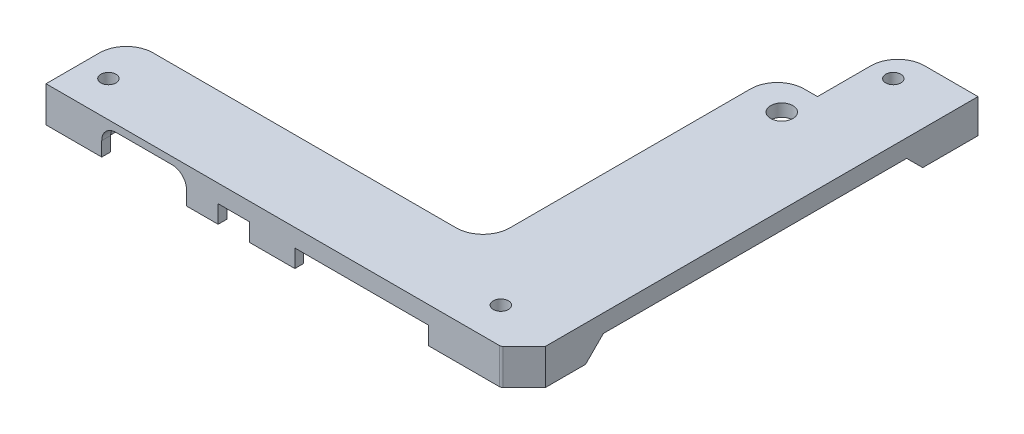
SolidWorks part; units mm, degrees
ref_plane "前视基准面" through (0, 0, 0) normal (0, 0, 1) x (1, 0, 0)
ref_plane "上视基准面" through (0, 0, 0) normal (0, 1, 0) x (1, 0, 0)
ref_plane "右视基准面" through (0, 0, 0) normal (1, 0, 0) x (0, 0, -1)
sketch "草图2" plane through (0, 0, 0) normal (0, 1, 0) x (1, 0, 0)
  line L0 (40, 41) -> (44.5, 41)
  line L1 (0, 0) -> (53.5, 0)
  line L2 (0, 0) -> (0, 8)
  line L3 (0, 8) -> (40, 8)
  line L6 (40, 8) -> (40, 41)
  line L7 (44.5, 50) -> (53.5, 50)
  line L8 (53.5, 0) -> (53.5, 50)
  line L9 (44.5, 41) -> (44.5, 50)
  dimension "D1" = 53.5
  dimension "D2" = 8
  dimension "D3" = 13.5
  dimension "D4" = 50
  dimension "D5" = 9
  dimension "D6" = 9
extrude "凸台-拉伸1" add sketch "草图2" along normal blind 2
sketch "草图3" plane through (0, 0, 0) normal (0, -1, 0) x (1, 0, 0)
  line L0 (0, 0) -> (53.5, 0) construction
  line L1 (6.25, 0) -> (15.75, 0)
  line L2 (6.25, 0) -> (6.25, -8)
  line L3 (6.25, -8) -> (15.75, -8)
  line L4 (15.75, 0) -> (15.75, -8)
  line L5 (40, -8) -> (0, -8) construction
  line L6 (0, -8) -> (0, 0) construction
  dimension "D1" = 9.5
  dimension "D2" = 6.25
extrude "切除-拉伸1" cut sketch "草图3" against normal blind 1.2
sketch "草图4" plane through (0, 0, 0) normal (0, -1, 0) x (1, 0, 0)
  line L0 (15.75, 0) -> (53.5, 0) construction
  line L1 (18.4, 0) -> (23.4, 0)
  line L2 (18.4, 0) -> (18.4, -5)
  line L3 (18.4, -5) -> (23.4, -5)
  line L4 (23.4, 0) -> (23.4, -5)
  line L5 (0, -8) -> (0, 0) construction
  dimension "D1" = 5
  dimension "D2" = 5
  dimension "D3" = 18.4
extrude "切除-拉伸2" cut sketch "草图4" against normal blind 1
sketch "草图5" plane through (0, 0, 0) normal (0, 0, 1) x (1, 0, 0)
  line L2 (0, 0) -> (0, -2)
  line L3 (0, -2) -> (6.25, -2)
  line L4 (6.25, 0) -> (6.25, -2)
  line L7 (15.75, -2) -> (18.4, -2)
  line L10 (23.4, 0) -> (23.4, -2)
  line L11 (23.4, -2) -> (27.9, -2)
  line L12 (15.75, 0) -> (18.4, 0)
  line L13 (18.4, 0) -> (18.4, 1)
  line L14 (18.4, 1) -> (23.4, 1)
  line L15 (23.4, 1) -> (23.4, 0)
  line L16 (23.4, 0) -> (53.5, 0)
  line L17 (53.5, 0) -> (53.5, 2)
  line L18 (53.5, 2) -> (0, 2)
  line L19 (0, 2) -> (0, 0)
  line L20 (0, 0) -> (6.25, 0)
  line L21 (6.25, 0) -> (6.25, 1.2)
  line L22 (6.25, 1.2) -> (15.75, 1.2)
  line L23 (15.75, 1.2) -> (15.75, 0)
  line L25 (18.4, -2) -> (18.4, 1)
  line L26 (18.4, 1) -> (23.4, 1)
  line L27 (23.4, 1) -> (23.4, 0)
  line L28 (27.9, 0) -> (42.9, 0)
  line L29 (53.5, 0) -> (53.5, 2)
  line L30 (53.5, 2) -> (0, 2)
  line L31 (0, 2) -> (0, 0)
  line L33 (6.25, 0) -> (6.25, 1.2)
  line L34 (6.25, 1.2) -> (15.75, 1.2)
  line L35 (15.75, 1.2) -> (15.75, -2)
  line L36 (27.9, 0) -> (27.9, -2)
  line L38 (42.9, 0) -> (42.9, -2)
  line L39 (42.9, -2) -> (53.5, -2)
  line L40 (53.5, 0) -> (53.5, -2)
  dimension "D2" = 4
  dimension "D3" = 15
  dimension "D4" = 27.9
  dimension "D1" = 0
extrude "凸台-拉伸2" add sketch "草图5" along normal blind 1
fillet "圆角1" radius 1.6 2 edges at (15.75, 1.2, -3.5) (6.25, 1.2, -3.5)
sketch "草图6" plane through (0, 0, 0) normal (0, -1, 0) x (1, 0, 0)
  line L0 (6.3008, -8) -> (0, -8) construction
  line L1 (53.5, 0) -> (44, 0)
  line L2 (53.5, 0) -> (53.5, -6)
  line L3 (53.5, -6) -> (44, -6)
  line L4 (44, 0) -> (44, -6)
  line L5 (44.5, -50) -> (53.5, -50)
  line L6 (44.5, -50) -> (44.5, -44)
  line L7 (44.5, -44) -> (53.5, -44)
  line L8 (53.5, -50) -> (53.5, -44)
  line L9 (0, 0) -> (4.6, 0)
  line L10 (0, 0) -> (0, -8)
  line L11 (0, -8) -> (4.6, -8)
  line L12 (4.6, 0) -> (4.6, -8)
  line L13 (53.5, 0) -> (53.5, -50) construction
  point P20 (0, -4)
  dimension "D1" = 6
  dimension "D2" = 6
  dimension "D3" = 9.5
  dimension "D4" = 4.6
extrude "凸台-拉伸3" add sketch "草图6" along normal blind 2
chamfer "倒角1" distance 2.5 angle 45 1 edges at (53.5, 0, 1)
chamfer "倒角2" distance 2 angle 45 2 edges at (49, 0, -44) (48.75, 0, -6)
fillet "圆角2" radius 3 4 edges at (0, 0, -8) (40, 1, -8) (40, 1, -41) (44.5, 0, -50)
sketch "草图7" plane through (0, -2, 0) normal (0, -1, 0) x (1, 0, 0)
  circle A0 centre (47, -3) radius 0.85
  circle A1 centre (47, -47) radius 0.85
  circle A2 centre (3, -3) radius 0.85
  dimension "D1" = 1.7
  dimension "D2" = 1.7
  dimension "D3" = 1.7
extrude "切除-拉伸3" cut sketch "草图7" against normal through all
sketch "草图8" plane through (0, 2, 0) normal (0, 1, 0) x (1, 0, 0)
  circle A0 centre (44, 37.5) radius 1.25
  dimension "D1" = 2.5
extrude "切除-拉伸4" cut sketch "草图8" against normal through all
sketch "草图9" plane through (0, 0, 0) normal (0, -1, 0) x (1, 0, 0)
  circle A0 centre (44, -37.5) radius 2.5
  dimension "D1" = 5
extrude "切除-拉伸5" cut sketch "草图9" against normal blind 0.6
fillet "圆角3" radius 0.4 1 edges at (51, 0, 1)
sketch "草图10" plane through (0, -2, 0) normal (0, -1, 0) x (1, 0, 0)
  line L1 (42.9582, -43.0369) -> (55.084, -43.0369)
  line L2 (42.9582, -43.0369) -> (42.9582, -51.3721)
  line L3 (42.9582, -51.3721) -> (55.084, -51.3721)
  line L4 (55.084, -43.0369) -> (55.084, -51.3721)
extrude "切除-拉伸6" cut sketch "草图10" against normal blind 0.2
sketch "草图11" plane through (0, 0, 1) normal (0, 0, 1) x (1, 0, 0)
  line L0 (23.4, 1) -> (23.4, -2) construction
  line L1 (18.4, 1) -> (23.4, 1) construction
  line L2 (18.4, -2) -> (18.4, 1) construction
  line L3 (23.4, 1) -> (23.4, -2)
  line L4 (18.4, 1) -> (23.4, 1)
  line L5 (18.4, -2) -> (18.4, 1)
  line L6 (18.4, -2) -> (19.3, -2)
  line L7 (22.8, -2) -> (23.4, -2)
  line L9 (19.3, -2) -> (19.3, 0)
  line L10 (19.3, 0) -> (22.8, 0)
  line L11 (22.8, -2) -> (22.8, 0)
  dimension "D1" = 1
  dimension "D2" = 0.9
  dimension "D3" = 0.6
extrude "凸台-拉伸4" add sketch "草图11" against normal blind 1
